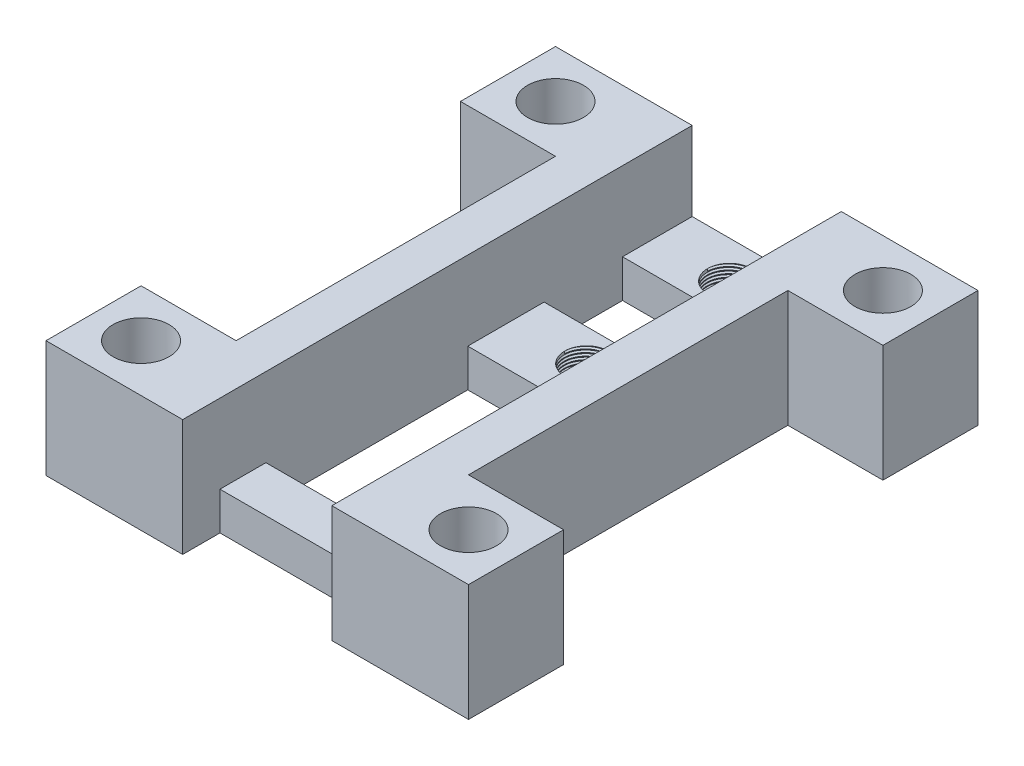
SolidWorks part; units mm, degrees
ref_plane "Front Plane" through (0, 0, 0) normal (0, 0, 1) x (1, 0, 0)
ref_plane "Top Plane" through (0, 0, 0) normal (0, 1, 0) x (1, 0, 0)
ref_plane "Right Plane" through (0, 0, 0) normal (1, 0, 0) x (0, 0, -1)
sketch "Sketch1" plane through (0, 0, 0) normal (0, 1, 0) x (1, 0, 0)
  line L0 (0, 0) -> (34, 0) construction
  line L1 (0, 0) -> (34, 0)
  line L2 (0, 0) -> (0, -41)
  line L3 (0, -41) -> (34, -41)
  line L4 (34, 0) -> (34, -41)
  line L5 (17, 0) -> (17, -18) construction
  line L6 (0, -20.5) -> (34, -20.5) construction
  line L7 (9.5, 0) -> (9.5, -7.65) construction
  line L8 (0, 0) -> (34, 0) construction
  line L9 (0, -7.65) -> (34, -7.65) construction
  line L10 (24.5, 0) -> (24.5, -7.65) construction
  line L11 (0, -33.35) -> (34, -33.35) construction
  line L12 (24.5, -41) -> (24.5, -33.35) construction
  line L13 (9.5, -41) -> (9.5, -33.35) construction
  line L14 (4.75, -33.35) -> (4.75, -41) construction
  line L15 (0, -7.65) -> (9.5, -7.65)
  line L16 (0, -7.65) -> (0, -33.35)
  line L17 (0, -33.35) -> (9.5, -33.35)
  line L18 (9.5, -7.65) -> (9.5, -33.35)
  line L19 (24.5, -7.65) -> (34, -7.65)
  line L20 (24.5, -7.65) -> (24.5, -33.35)
  line L21 (24.5, -33.35) -> (34, -33.35)
  line L22 (34, -7.65) -> (34, -33.35)
  line L23 (9.5, -37.175) -> (0, -37.175) construction
  line L24 (27.9452, -39.435) -> (26.6404, -37.175)
  line L25 (7.3596, -37.175) -> (6.0548, -34.915)
  line L26 (6.0548, -34.915) -> (3.4452, -34.915)
  line L27 (3.4452, -34.915) -> (2.1404, -37.175)
  line L28 (2.1404, -37.175) -> (3.4452, -39.435)
  line L29 (3.4452, -39.435) -> (6.0548, -39.435)
  line L30 (6.0548, -39.435) -> (7.3596, -37.175)
  line L31 (30.5548, -39.435) -> (27.9452, -39.435)
  line L32 (31.8596, -37.175) -> (30.5548, -39.435)
  line L33 (30.5548, -34.915) -> (31.8596, -37.175)
  line L34 (27.9452, -34.915) -> (30.5548, -34.915)
  line L35 (26.6404, -37.175) -> (27.9452, -34.915)
  line L36 (30.5548, -1.565) -> (27.9452, -1.565)
  line L37 (31.8596, -3.825) -> (30.5548, -1.565)
  line L38 (30.5548, -6.085) -> (31.8596, -3.825)
  line L39 (27.9452, -6.085) -> (30.5548, -6.085)
  line L40 (26.6404, -3.825) -> (27.9452, -6.085)
  line L41 (27.9452, -1.565) -> (26.6404, -3.825)
  line L42 (6.0548, -1.565) -> (7.3596, -3.825)
  line L43 (3.4452, -1.565) -> (6.0548, -1.565)
  line L44 (2.1404, -3.825) -> (3.4452, -1.565)
  line L45 (3.4452, -6.085) -> (2.1404, -3.825)
  line L46 (6.0548, -6.085) -> (3.4452, -6.085)
  line L47 (7.3596, -3.825) -> (6.0548, -6.085)
  line L48 (27.9452, -1.565) -> (24.5, -1.565) construction
  circle A0 centre (4.75, -37.175) radius 2.26 construction
  dimension "D7" = 4.52
  dimension "D1" = 41
  dimension "D2" = 34
  dimension "D3" = 17
  dimension "D4" = 17
  dimension "D5" = 7.5
  dimension "D6" = 7.65
extrude "Boss-Extrude1" add sketch "Sketch1" along normal blind 14.4 contours L2 L1 L4 L3
sketch "Sketch2" plane through (0, 14.4, 0) normal (0, 1, 0) x (1, 0, 0)
  line L0 (17, 0) -> (17, -41) construction
  line L1 (0, 0) -> (34, 0) construction
  line L2 (0, -41) -> (34, -41) construction
  line L3 (17, -41) -> (17, -20.5) construction
  line L4 (17, -20.5) -> (34, -20.5) construction
  line L5 (34, 0) -> (34, -41) construction
  line L6 (34, -20.5) -> (0, -20.5) construction
  line L7 (0, 0) -> (0, -41) construction
  line L10 (0, -7.65) -> (34, -7.65) construction
  line L11 (34, 0) -> (34, -7.65) construction
  line L12 (0, 0) -> (34, 0) construction
  line L13 (7.65, 0) -> (7.65, -7.65) construction
  line L14 (26.35, 0) -> (26.35, -7.65) construction
  line L15 (26.35, -41) -> (26.35, -33.35) construction
  line L16 (7.65, -41) -> (7.65, -33.35) construction
  line L17 (0, -33.35) -> (34, -33.35) construction
  line L18 (7.65, -37.175) -> (0, -37.175) construction
  line L19 (3.825, -37.175) -> (3.825, -7.65) construction
  line L20 (3.825, -7.65) -> (3.825, 0) construction
  line L21 (7.65, -3.825) -> (0, -3.825) construction
  line L22 (7.65, -13.9059) -> (26.35, -13.9059) construction
  line L23 (0, -7.65) -> (7.65, -7.65)
  line L24 (0, -7.65) -> (0, -33.35)
  line L25 (0, -33.35) -> (7.65, -33.35)
  line L26 (7.65, -7.65) -> (7.65, -33.35)
  line L27 (26.35, -7.65) -> (34, -7.65)
  line L28 (26.35, -7.65) -> (26.35, -33.35)
  line L29 (26.35, -33.35) -> (34, -33.35)
  line L30 (34, -7.65) -> (34, -33.35)
  line L31 (9.95, 0) -> (9.95, -41) construction
  line L32 (24.05, 0) -> (24.05, -41) construction
  line L33 (6.075, -3.825) -> (27.925, -3.825) construction
  line L34 (0, -3.825) -> (1.575, -3.825) construction
  line L35 (34, -3.825) -> (32.425, -3.825) construction
  circle A0 centre (3.825, -3.825) radius 2.25
  circle A1 centre (30.175, -3.825) radius 2.25
  circle A2 centre (30.175, -37.175) radius 2.25
  circle A3 centre (3.825, -37.175) radius 2.25
  dimension "D3" = 18.7
  dimension "D1" = 7.65
  dimension "D2" = 7.65
  dimension "D4" = 2.3
  dimension "D5" = 14.1
  dimension "D6" = 21.85
  dimension "D7" = 1.575
  dimension "D8" = 1.575
  dimension "D9" = 34
  dimension "D10" = 7.65
  dimension "D11" = 41
extrude "Cut-Extrude1" cut sketch "Sketch2" against normal through all
sketch "Sketch3" plane through (0, 14.4, 0) normal (0, 1, 0) x (1, 0, 0)
  line L0 (17, 0) -> (17, -41) construction
  line L1 (0, 0) -> (34, 0) construction
  line L2 (0, -41) -> (34, -41) construction
  line L3 (11, 0) -> (11, -41) construction
  line L4 (23, 0) -> (23, -41) construction
  line L5 (7.65, -33.35) -> (7.65, -7.65) construction
  line L10 (26.35, -7.65) -> (26.35, -33.35) construction
  line L12 (11, 0) -> (23, 0)
  line L13 (11, 0) -> (11, -41)
  line L14 (11, -41) -> (23, -41)
  line L15 (23, 0) -> (23, -41)
  dimension "D1" = 3.35
  dimension "D2" = 3.35
extrude "Cut-Extrude2" cut sketch "Sketch3" against normal blind 6.35
sketch "Sketch4" plane through (0, 8.05, 0) normal (0, 1, 0) x (1, 0, 0)
  line L0 (17, 0) -> (17, -41) construction
  line L1 (23, 0) -> (11, 0) construction
  line L2 (11, -41) -> (23, -41) construction
  line L3 (13.25, -23) -> (13.25, -26.75)
  line L4 (23, 0) -> (11, 0) construction
  line L5 (14.8975, -18.5) -> (14.8975, -27.5) construction
  line L6 (17, -41) -> (17, -27.5) construction
  line L7 (17, 0) -> (17, -18.5) construction
  line L8 (17, -18.5) -> (17, -27.5) construction
  line L9 (17, -18.5) -> (9.35, -18.5) construction
  line L10 (20.75, -23) -> (20.75, -26.75)
  line L11 (9.35, -27.5) -> (17, -27.5) construction
  line L13 (11, 0) -> (23, 0) construction
  line L14 (20.75, -26.75) -> (20.5, -26.75)
  line L15 (13.25, -26.75) -> (20.5, -26.75) construction
  line L17 (13.25, -23) -> (20.75, -23) construction
  line L18 (20.75, -23) -> (17, -19.25) construction
  line L19 (17, -19.25) -> (13.25, -23) construction
  line L20 (13.25, -23) -> (17, -26.75) construction
  line L21 (17, -26.75) -> (20.75, -23) construction
  line L23 (20.5, -26.75) -> (13.25, -26.75)
  arc A1 (13.25, -23) -> (20.75, -23) centre (17, -23) cw
  dimension "D4" = 12
  dimension "D1" = 27.5
  dimension "D2" = 18.5
  dimension "D3" = 9
sketch "Sketch8" plane through (0, 8.05, 0) normal (0, 1, 0) x (1, 0, 0)
  line L0 (11, 0) -> (23, 0) construction
  line L1 (11, -6) -> (23, -6) construction
  line L2 (11, 0) -> (11, -41) construction
  line L4 (23, -41) -> (23, 0) construction
  line L6 (17, -6) -> (17, -11.5) construction
  line L7 (23, -11.5) -> (11, -11.5) construction
  line L13 (11, -6) -> (23, -6)
  line L14 (11, -6) -> (11, -11.5)
  line L15 (11, -11.5) -> (23, -11.5)
  line L16 (23, -6) -> (23, -11.5)
  dimension "D1" = 6
  dimension "D2" = 5.5
extrude "Cut-Extrude5" cut sketch "Sketch8" against normal through all
extrude "Cut-Extrude6" cut sketch "Sketch4" against normal through all
sketch "Sketch11" plane through (0, 0, 0) normal (0, 0, -1) x (-1, 0, 0)
  line L0 (-34, 14.4) -> (-34, 0) construction
  line L1 (-34, 5) -> (0, 5)
  line L2 (-34, 5) -> (-34, 0)
  line L3 (-34, 0) -> (0, 0)
  line L4 (0, 5) -> (0, 0)
  dimension "D1" = 5
extrude "Cut-Extrude7" cut sketch "Sketch11" against normal through all
sketch "Sketch12" plane through (0, 8.05, 0) normal (0, 1, 0) x (1, 0, 0)
  line L0 (17, -11.5) -> (17, -12.75) construction
  line L1 (11, -11.5) -> (23, -11.5) construction
  line L2 (17, -12.75) -> (17, -16.25) construction
  line L3 (23, -6) -> (23, -11.5) construction
  line L4 (23, -8.75) -> (11, -8.75) construction
  line L5 (11, 0) -> (11, -41) construction
  circle A0 centre (17, -14.5) radius 1.7571
  circle A1 centre (17, -3) radius 1.7571
  dimension "D1" = 1.25
  dimension "D2" = 3.5
extrude "Cut-Extrude8" cut sketch "Sketch12" against normal through all
thread "Thread1" pitch 0.25 method cut profile "Thread Profile1" start angle 0, offset 0, length 2, pitch 0.25, diameter 3.5141
ref_plane "Plane1" through (15.2429, 8.05, 3) normal (0, 0, 1) x (-1, 0, 0)
sketch "Thread Profile1" plane through (15.2429, 8.05, 3) normal (0, 0, 1) x (-1, 0, 0)
  line L0 (0, 0) -> (0, 0.25) construction
  line L1 (0, 0) -> (0.1353, 0.0781)
  line L2 (0.1353, 0.0781) -> (0.1353, 0.1094)
  line L3 (0.1353, 0.1094) -> (0, 0.1875)
  line L4 (0.1353, 0.0937) -> (0, 0.0937) construction
  line L11 (0, 0) -> (0, 0.1875)
  point P2 (0, 0)
  dimension "Pitch" = 0.25
  dimension "Profile_Angle" = 60
  dimension "Profile_Land" = 0.0312
  dimension "Profile_Height" = 0.1353
thread "Thread2" pitch 0.25 method cut profile "Thread Profile2" start angle 0, offset 0, length 2, pitch 0.25, diameter 3.5141
ref_plane "Plane2" through (15.2429, 8.05, 14.5) normal (0, 0, 1) x (-1, 0, 0)
sketch "Thread Profile2" plane through (15.2429, 8.05, 14.5) normal (0, 0, 1) x (-1, 0, 0)
  line L0 (0, 0) -> (0, 0.25) construction
  line L1 (0, 0) -> (0.1353, 0.0781)
  line L2 (0.1353, 0.0781) -> (0.1353, 0.1094)
  line L3 (0.1353, 0.1094) -> (0, 0.1875)
  line L4 (0.1353, 0.0937) -> (0, 0.0937) construction
  line L11 (0, 0) -> (0, 0.1875)
  point P2 (0, 0)
  dimension "Pitch" = 0.25
  dimension "Profile_Angle" = 60
  dimension "Profile_Land" = 0.0312
  dimension "Profile_Height" = 0.1353
sketch "Sketch17" plane through (0, 8.05, 0) normal (0, 1, 0) x (1, 0, 0)
  line L0 (17, -41) -> (17, -38) construction
  line L5 (13.25, -26.75) -> (13.25, -27.95) construction
  line L6 (11, -27.95) -> (16.4, -27.95) construction
  line L7 (11, 0) -> (11, -41) construction
  line L8 (16.4, -27.95) -> (16.4, -33.95) construction
  line L9 (16.4, -33.95) -> (11, -33.95) construction
  line L10 (11, -27.95) -> (16.4, -27.95)
  line L11 (11, -27.95) -> (11, -33.95)
  line L12 (11, -33.95) -> (16.4, -33.95)
  line L13 (16.4, -27.95) -> (16.4, -33.95)
  line L14 (11, -41) -> (23, -41) construction
  line L16 (11, -38) -> (23, -38)
  line L17 (11, -38) -> (11, -41)
  line L18 (11, -41) -> (23, -41)
  line L19 (23, -38) -> (23, -41)
  dimension "D1" = 1.2
  dimension "D2" = 5.4
  dimension "D3" = 6
  dimension "D4" = 3
extrude "Cut-Extrude9" cut sketch "Sketch17" against normal through all contours L11 L10 L13 L12 | L17 L16 L19 L18
sketch "Sketch18" plane through (0, 8.05, 0) normal (0, 1, 0) x (1, 0, 0)
  line L0 (11, -11.5) -> (11, -27.95) construction
  line L1 (11, -18.0606) -> (23, -18.0606)
  line L2 (11, -18.0606) -> (11, -34.3042)
  line L3 (11, -34.3042) -> (23, -34.3042)
  line L4 (23, -18.0606) -> (23, -34.3042)
  line L5 (23, -38) -> (23, -11.5) construction
extrude "Cut-Extrude10" cut sketch "Sketch18" against normal blind 10
sketch "Sketch19" plane through (0, 8.05, 0) normal (0, 1, 0) x (1, 0, 0)
  line L0 (11, 0) -> (11, -41) construction
  line L1 (11, -5.6052) -> (23, -5.6052)
  line L2 (11, -5.6052) -> (11, -11.919)
  line L3 (11, -11.919) -> (23, -11.919)
  line L4 (23, -5.6052) -> (23, -11.919)
  line L5 (23, -18.0606) -> (23, -11.5) construction
extrude "Cut-Extrude11" cut sketch "Sketch19" against normal blind 10
